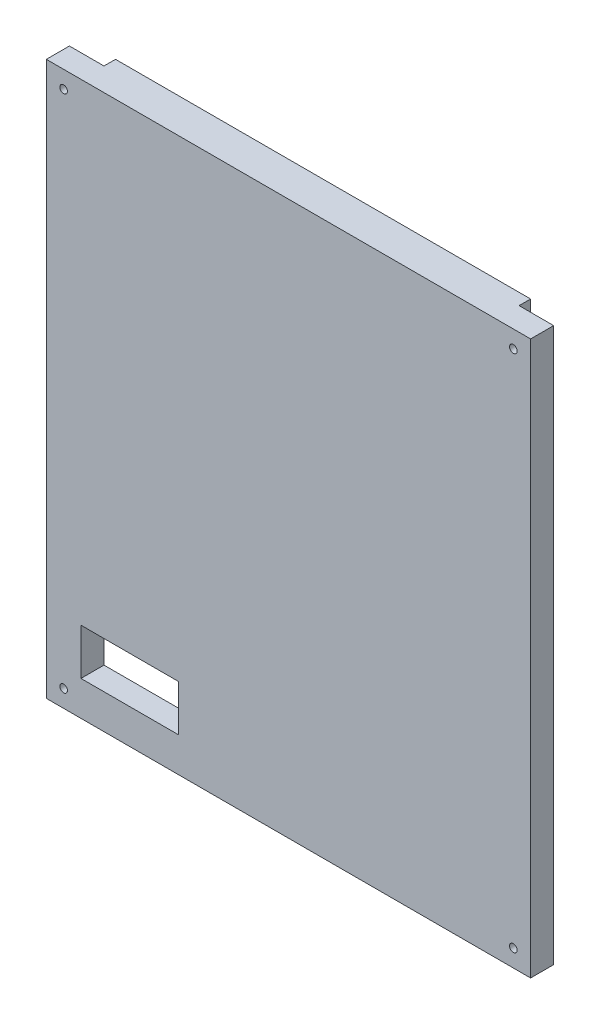
SolidWorks part; units mm, degrees
ref_plane "Front Plane" through (0, 0, 0) normal (0, 0, 1) x (1, 0, 0)
ref_plane "Top Plane" through (0, 0, 0) normal (0, 1, 0) x (1, 0, 0)
ref_plane "Right Plane" through (0, 0, 0) normal (1, 0, 0) x (0, 0, -1)
sketch "Sketch3" plane through (0, 0, 0) normal (0, 1, 0) x (1, 0, 0)
  line L0 (-105, 0) -> (105, 0)
  line L1 (105, 0) -> (105, -10)
  line L2 (105, -10) -> (-105, -10)
  line L3 (-105, -10) -> (-105, 0)
  dimension "D1" = 210
  dimension "D2" = 10
extrude "Boss-Extrude1" add sketch "Sketch3" along normal blind 240
ref_plane "Plane1" through (0, 45, 0) normal (0, 1, 0) x (1, 0, 0)
sketch "Sketch5" plane through (0, 240, 0) normal (0, 1, 0) x (1, 0, 0)
  line L0 (-90, 0) -> (-90, 5)
  line L1 (105, 0) -> (-105, 0) construction
  line L2 (-90, 5) -> (90, 5)
  line L3 (90, 5) -> (90, 0)
  line L4 (-105, 0) -> (-105, -10) construction
  line L5 (105, 0) -> (90, 0)
  line L9 (-105, 0) -> (-105, -10)
  line L10 (-105, -10) -> (105, -10)
  line L11 (105, -10) -> (105, 0)
  line L12 (105, 0) -> (-105, 0)
  line L13 (-105, 0) -> (-105, -10)
  line L14 (-105, -10) -> (105, -10)
  line L15 (105, -10) -> (105, 0)
  line L16 (-90, 0) -> (-105, 0)
  dimension "D1" = 180
  dimension "D2" = 5
  dimension "D3" = 15
  dimension "D4" = 0
extrude "Boss-Extrude2" add sketch "Sketch5" against normal up to surface (195 mm away) up to plane "Plane1"
sketch "Sketch6" plane through (0, 45, 0) normal (0, 1, 0) x (1, 0, 0)
  line L0 (-50, 0) -> (-50, 15)
  line L2 (-50, 15) -> (50, 15)
  line L3 (50, 15) -> (50, 0)
  line L4 (50, 0) -> (-50, 0)
  line L6 (90, 5) -> (-90, 5) construction
  dimension "D1" = 100
  dimension "D2" = 10
extrude "Boss-Extrude3" add sketch "Sketch6" against normal blind 10
sketch "Sketch7" plane through (0, 0, 10) normal (0, 0, 1) x (1, 0, 0)
  line L0 (0, -1000) -> (0, 49000) construction
  line L1 (-105, 240) -> (105, 240) construction
  line L2 (-105, 240) -> (-105, 0) construction
  line L3 (55, 0) -> (-55, 0) construction
  circle A0 centre (-97.5, 232.5) radius 1.65
  circle A1 centre (-97.5, 7.5) radius 1.65
  circle A2 centre (97.5, 7.5) radius 1.65
  circle A3 centre (97.5, 232.5) radius 1.65
  dimension "D1" = 3.3
  dimension "D2" = 7.5
  dimension "D4" = 7.5
  dimension "D3" = 7.5
  dimension "D5" = 7.5
extrude "Cut-Extrude1" cut sketch "Sketch7" against normal up to surface (10 mm away) up to face at (0, 100.8333, 0)
sketch "Sketch8" plane through (0, 0, 10) normal (0, 0, 1) x (1, 0, 0)
  line L0 (-105, 240) -> (-105, 0) construction
  line L1 (-90, 35) -> (-47.75, 35)
  line L2 (-90, 35) -> (-90, 15)
  line L3 (-90, 15) -> (-47.75, 15)
  line L4 (-47.75, 35) -> (-47.75, 15)
  line L5 (-105, 0) -> (105, 0) construction
  line L6 (0, -1000) -> (0, 49000) construction
  line L7 (90, 15) -> (47.75, 15)
  line L8 (47.75, 35) -> (47.75, 15)
  line L9 (90, 35) -> (47.75, 35)
  line L10 (90, 35) -> (90, 15)
  dimension "D1" = 15
  dimension "D2" = 15
  dimension "D3" = 42.25
  dimension "D4" = 20
extrude "Cut-Extrude2" cut sketch "Sketch8" against normal up to surface (10 mm away) contours L4 L1 L2 L3 region at (-68.875, 25, 10) up to face at (99.15, 232.5, 0)
